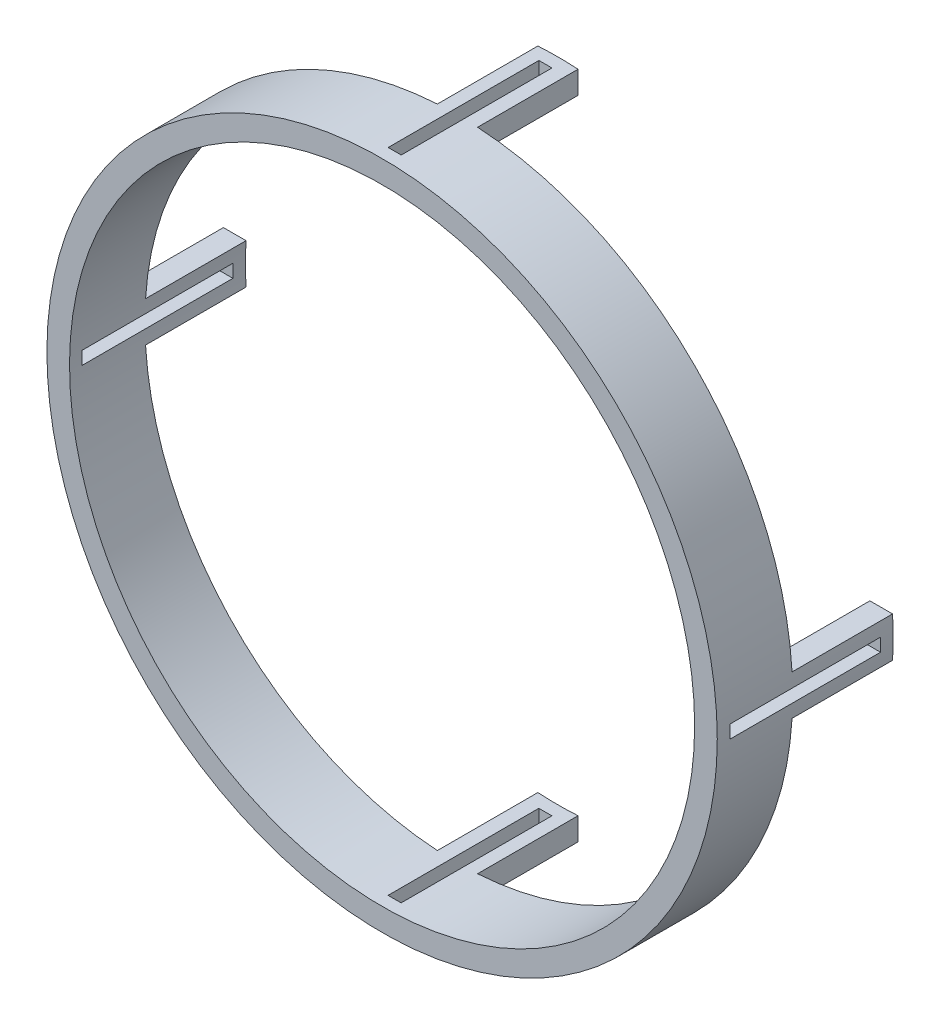
SolidWorks part; units mm, degrees
ref_plane "Front Plane" through (0, 0, 0) normal (0, 0, 1) x (1, 0, 0)
ref_plane "Top Plane" through (0, 0, 0) normal (0, 1, 0) x (1, 0, 0)
ref_plane "Right Plane" through (0, 0, 0) normal (1, 0, 0) x (0, 0, -1)
sketch "Sketch1" plane through (0, 0, 0) normal (0, 0, 1) x (1, 0, 0)
  circle A0 centre (0, 0) radius 78.994
  circle A1 centre (0, 0) radius 84.709
  dimension "D1" = 157.988
  dimension "D2" = 169.418
extrude "Boss-Extrude1" add sketch "Sketch1" along normal blind 19.05
sketch "Sketch3" plane through (0, 0, 0) normal (0, 0, -1) x (-1, 0, 0)
  line L0 (30.8173, 0) -> (-22.3005, 0) construction
  line L1 (0, -12.9993) -> (0, 95.4691) construction
  line L2 (-5.08, 78.8305) -> (-5.08, 84.5565)
  line L3 (5.08, 78.8305) -> (5.08, 84.5565)
  line L4 (-5.08, -78.8305) -> (-5.08, -84.5565)
  line L5 (5.08, -78.8305) -> (5.08, -84.5565)
  line L6 (0, 0) -> (44.2484, -44.2484) construction
  line L7 (78.8305, -5.08) -> (84.5565, -5.08)
  line L8 (78.8305, 5.08) -> (84.5565, 5.08)
  line L9 (-78.8305, 5.08) -> (-84.5565, 5.08)
  line L10 (-78.8305, -5.08) -> (-84.5565, -5.08)
  arc A0 (5.08, 78.8305) -> (-5.08, 78.8305) centre (0, 0) ccw
  circle A2 centre (0, 0) radius 78.994 construction
  arc A3 (5.08, 84.5565) -> (-5.08, 84.5565) centre (0, 0) ccw
  circle A4 centre (0, 0) radius 84.709 construction
  arc A5 (5.08, -78.8305) -> (-5.08, -78.8305) centre (0, 0) cw
  arc A6 (5.08, -84.5565) -> (-5.08, -84.5565) centre (0, 0) cw
  arc A7 (84.5565, -5.08) -> (84.5565, 5.08) centre (0, 0) ccw
  arc A8 (78.8305, -5.08) -> (78.8305, 5.08) centre (0, 0) ccw
  arc A9 (-78.8305, -5.08) -> (-78.8305, 5.08) centre (0, 0) cw
  arc A10 (-84.5565, -5.08) -> (-84.5565, 5.08) centre (0, 0) cw
  dimension "D1" = 5.08
  dimension "D2" = 5.08
  dimension "D3" = 5.08
  dimension "D4" = 5.08
  dimension "D5" = 45
extrude "Boss-Extrude2" add sketch "Sketch3" along normal blind 25.4
sketch "Sketch2" plane through (0, 0, 0) normal (0, 1, 0) x (1, 0, 0)
  line L0 (5.08, 25.4) -> (-5.08, 25.4) construction
  line L1 (0, -2.0807) -> (0, -15.8358) construction
  line L3 (-1.651, -15.875) -> (1.651, -15.875)
  line L4 (-1.651, -15.875) -> (-1.651, 22.225)
  line L5 (-1.651, 22.225) -> (1.651, 22.225)
  line L6 (1.651, -15.875) -> (1.651, 22.225)
  line L7 (-1.651, -15.875) -> (1.651, 22.225) construction
  line L8 (-1.651, 22.225) -> (1.651, -15.875) construction
  point P0 (0, 3.175)
  point P10 (0, 25.4)
  dimension "D1" = 3.302
  dimension "D2" = 38.1
  dimension "D3" = 3.175
ref_axis "Axis1" through (0, 0, 2.0807) along (0, 0, 1)
extrude "Cut-Extrude1" cut sketch "Sketch2" against normal through all
pattern_circular "CirPattern1" count 4 over 360 about axis through (0, 0, 2.0807) along (0, 0, 1) of "Cut-Extrude1"
